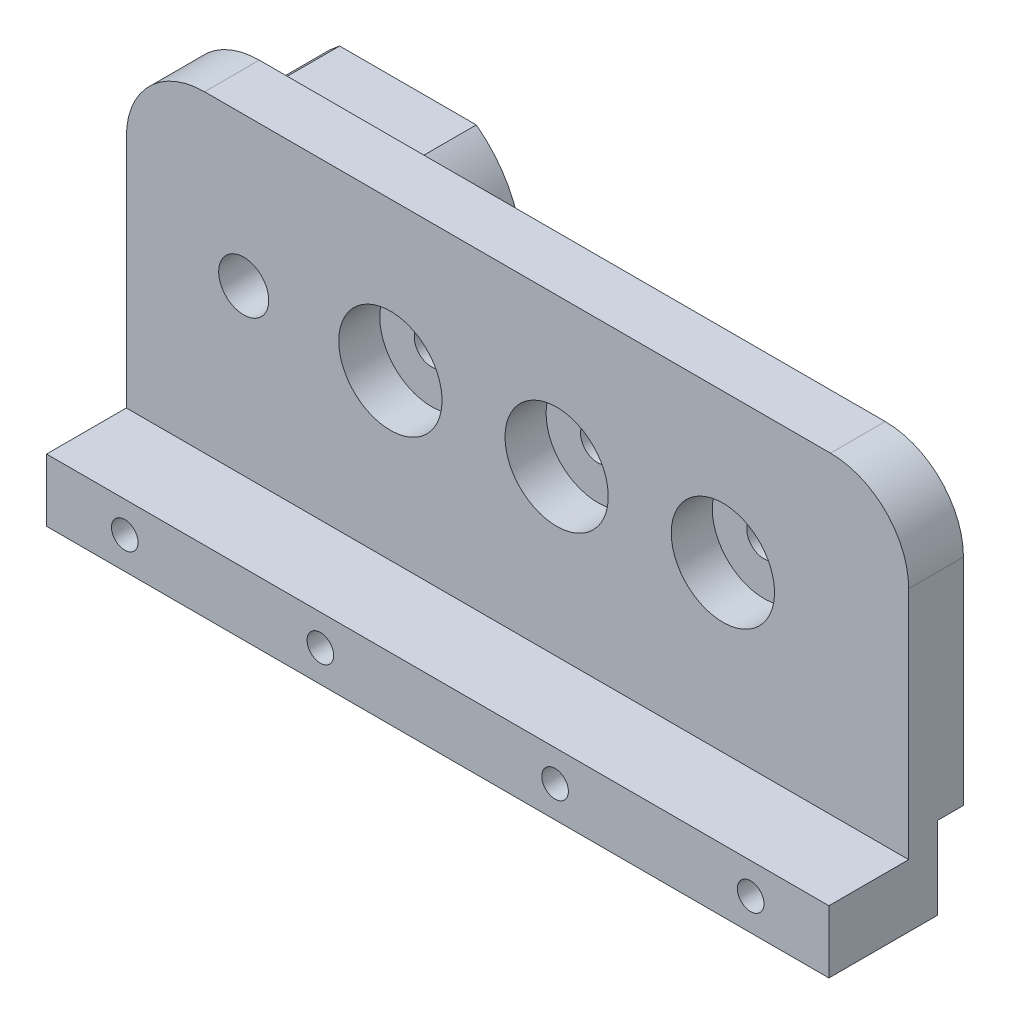
SolidWorks part; units mm, degrees
ref_plane "Front Plane" through (0, 0, 0) normal (0, 0, 1) x (1, 0, 0)
ref_plane "Top Plane" through (0, 0, 0) normal (0, 1, 0) x (1, 0, 0)
ref_plane "Right Plane" through (0, 0, 0) normal (1, 0, 0) x (0, 0, -1)
sketch "Sketch1" plane through (0, 0, 0) normal (0, 0, 1) x (1, 0, 0)
  line L1 (0, 0) -> (100, 0)
  line L2 (0, 0) -> (0, 48)
  line L3 (0, 48) -> (100, 48)
  line L4 (100, 0) -> (100, 48)
  dimension "D1" = 100
  dimension "D2" = 48
extrude "Boss-Extrude1" add sketch "Sketch1" along normal blind 7
sketch "Sketch2" plane through (0, 0, 7) normal (0, 0, 1) x (1, 0, 0)
  line L0 (0, 0) -> (100, 0) construction
  line L1 (0, 48) -> (0, 0) construction
  circle A0 centre (15, 29) radius 3.2
  circle A1 centre (33.75, 29) radius 2.2
  circle A2 centre (55, 29) radius 2.2
  circle A3 centre (76.25, 29) radius 2.2
  dimension "D1" = 4.4
  dimension "D2" = 18.75
  dimension "D3" = 21.25
  dimension "D4" = 21.25
  dimension "D5" = 29
  dimension "D6" = 15
  dimension "D7" = 6.4
extrude "Cut-Extrude1" cut sketch "Sketch2" against normal up to next
sketch "Sketch3" plane through (0, 0, 0) normal (0, 0, -1) x (-1, 0, 0)
  line L0 (0, 48) -> (0, 0) construction
  line L1 (-100, 0) -> (0, 0)
  line L2 (-100, 0) -> (-100, 8)
  line L3 (-100, 8) -> (0, 8)
  line L4 (0, 0) -> (0, 8)
  dimension "D1" = 8
extrude "Boss-Extrude2" add sketch "Sketch3" along normal blind 10.2
sketch "Sketch4" plane through (0, 0, 0) normal (0, 0, -1) x (-1, 0, 0)
  circle A0 centre (-76.25, 29) radius 6.6
  circle A1 centre (-55, 29) radius 6.6
  circle A2 centre (-33.75, 29) radius 6.6
  dimension "D1" = 13.2
extrude "Cut-Extrude2" cut sketch "Sketch4" against normal blind 5.25
sketch "Sketch5" plane through (0, 0, 7) normal (0, 0, 1) x (1, 0, 0)
  line L0 (35, 4.0521) -> (65, 4) construction
  line L1 (0, 0) -> (100, 0) construction
  circle A0 centre (35, 4.0521) radius 2.6
  circle A1 centre (65, 4) radius 2.6
  point P6 (50, 0)
  point P7 (50, 4.0261)
  dimension "D1" = 5.2
  dimension "D2" = 30
  dimension "D3" = 4
extrude "Cut-Extrude3" cut sketch "Sketch5" against normal blind 0.1
sketch "Sketch7" plane through (0, 0, 6.9) normal (0, 0, 1) x (1, 0, 0)
  circle A0 centre (35, 4.0521) radius 1.7
  circle A1 centre (65, 4) radius 1.7
  dimension "D1" = 3.4
extrude "Cut-Extrude4" cut sketch "Sketch7" against normal through all
sketch "Sketch8" plane through (0, 0, 7) normal (0, 0, 1) x (1, 0, 0)
  line L0 (10, 4.0521) -> (35, 4.0521) construction
  line L1 (0, 48) -> (0, 0) construction
  line L2 (100, 0) -> (100, 48) construction
  circle A0 centre (10, 4.0521) radius 1.7
  circle A1 centre (90, 4.0521) radius 1.7
  dimension "D1" = 3.4
  dimension "D2" = 10
  dimension "D3" = 10
extrude "Cut-Extrude5" cut sketch "Sketch8" against normal up to next
mirror "Mirror1" about plane through (0, 0, -10.2) normal (0, 0, 1) of bodies 110
delete or keep bodies "Body-Delete/Keep 1" type delete bodies bodies 110
sketch "Sketch9" plane through (100, 0, 0) normal (1, 0, 0) x (0, 0, -1)
  line L1 (27.4, 0) -> (24.1, 0)
  line L2 (27.4, 0) -> (27.4, 10.5)
  line L3 (27.4, 10.5) -> (24.1, 10.5)
  line L4 (24.1, 0) -> (24.1, 10.5)
  dimension "D1" = 10.5
  dimension "D2" = 3.3
extrude "Cut-Extrude6" cut sketch "Sketch9" against normal up to next
sketch "Sketch10" plane through (0, 0, -27.4) normal (0, 0, -1) x (-1, 0, 0)
  line L1 (-22.8594, 38.2) -> (-7.1406, 38.2)
  line L2 (-22.8594, 38.2) -> (-22.8594, 19.8) construction
  line L3 (-22.8594, 19.8) -> (-7.1406, 19.8)
  line L4 (-7.1406, 38.2) -> (-7.1406, 19.8) construction
  line L5 (-22.8594, 38.2) -> (-7.1406, 19.8) construction
  line L6 (-22.8594, 19.8) -> (-7.1406, 38.2) construction
  circle A0 centre (-15, 29) radius 12.1
  circle M6 centre (-15, 29) radius 3.2
  dimension "D2" = 24.2
  dimension "D1" = 18.4
extrude "Boss-Extrude3" add sketch "Sketch10" along normal blind 14 separate body contours L1 A0 L3 M6 | M6 region at (15, 37.896, -27.4) region at (15, 29, -27.4)
shell "Shell1" thickness 2.5 removed face at (15, 29, -27.4) removed face at (15, 29, -41.4) outward yes
combine bodies "Combine1" operation type add bodies to combine 115 116
fillet "Fillet3" radius 10 2 edges at (0, 48, -23.9) (100, 48, -23.9)
sketch "Sketch11" plane through (0, 0, -24.1) normal (0, 0, -1) x (-1, 0, 0)
  line L0 (-60.9585, 4) -> (-60.9585, 0)
  line L1 (-62.9793, 0.5) -> (-60.9585, 4)
  line L2 (-60.9585, 4) -> (-62.9793, 7.5)
  line L3 (-62.9793, 7.5) -> (-67.0207, 7.5)
  line L4 (-67.0207, 7.5) -> (-69.0414, 4)
  line L5 (-69.0414, 4) -> (-67.0207, 0.5)
  line L6 (-67.0207, 0.5) -> (-62.9793, 0.5)
  line L7 (0, 0) -> (-100, 0) construction
  line L8 (-69.0414, 4) -> (-69.0414, 0)
  line L9 (-60.9585, 0) -> (-69.0414, 0)
  circle A0 centre (-65, 4) radius 3.5 construction
  line M10 (-100, 0) -> (0, 0)
  circle M11 centre (-65, 4) radius 1.7
  dimension "D1" = 7
extrude "Cut-Extrude7" cut sketch "Sketch11" against normal blind 3.2 from offset 3 contours L5 L6 L1 L2 L3 L4 M11 | L5 L8 L0 L1 L6 M10 region at (61.0487, 2, -24.1) region at (62.0615, 2.3035, -24.1) offset against normal yes
